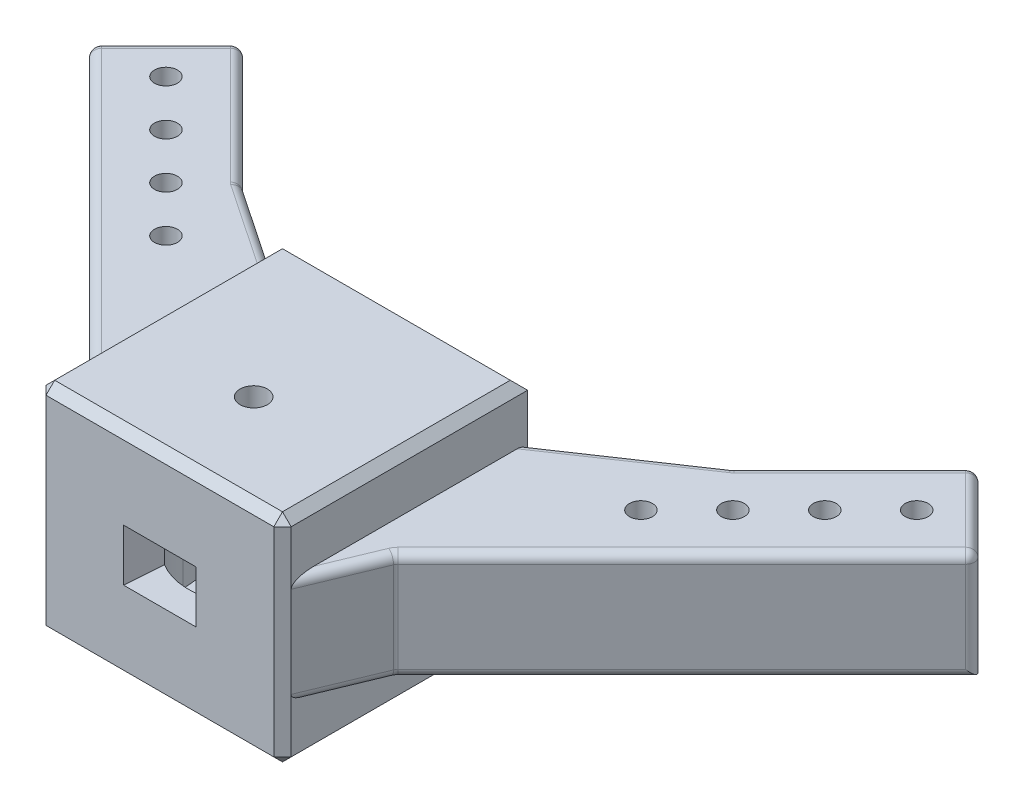
SolidWorks part; units mm, degrees
material "ABS"
ref_plane "前视基准面" through (0, 0, 0) normal (0, 0, 1) x (1, 0, 0)
ref_plane "上视基准面" through (0, 0, 0) normal (0, 1, 0) x (1, 0, 0)
ref_plane "右视基准面" through (0, 0, 0) normal (1, 0, 0) x (0, 0, -1)
other "Configuration Table"
sketch "草图1" plane through (0, 0, 0) normal (0, 1, 0) x (1, 0, 0)
  line L0 (0, 0) -> (0, -50000) construction
  line L1 (14.9366, -8.0239) -> (18.2843, 28.2843)
  line L2 (-28.2843, 28.2843) -> (28.2843, 28.2843)
  line L3 (-28.2843, 28.2843) -> (-28.2843, -28.2843)
  line L4 (-28.2843, -28.2843) -> (28.2843, -28.2843)
  line L5 (28.2843, 28.2843) -> (28.2843, -28.2843)
  line L6 (0, -28.2843) -> (0, 28.2843) construction
  line L7 (-28.2843, 0) -> (28.2843, 0) construction
  line L8 (-14.9366, -8.0239) -> (-18.2843, 28.2843)
  line L9 (-7.75, -19.4895) -> (-8.365, -28.2843)
  line L10 (7.75, -19.4895) -> (8.365, -28.2843)
  circle A0 centre (0, -6.6467) radius 3.15
  circle A1 centre (0, -6.6467) radius 15
  point P4 (0, 0)
  dimension "D1" = 6.3
  dimension "D2" = 30
  dimension "D3" = 56.5685
  dimension "D4" = 10.536
  dimension "D5" = 10
  dimension "D6" = 15.5
  dimension "D7" = 4
extrude "凸台-拉伸1" add sketch "草图1" along normal mid plane 50 contours A1 L8 L2 L3 L4 L5 L1 | A1 L1 L2 L8 | A1 A0 | A1 L8 L2 L3 L4 L9 | A1 L9 L4 L10 region at (0, 0, -16.4586) region at (20.9642, 0, 3.6641) region at (12.3502, 0, 14.3878) region at (0, 0, 24.6241) region at (-20.9642, 0, 3.6641)
extrude "切除-拉伸1" cut sketch "草图1<3>" against normal mid plane 40.3 contours A1 L1 L2 L8 | A1 A0 region at (0, 0, -16.4586) region at (12.3502, 0, 14.3878)
sketch "草图1<3>" plane through (0, 0, 0) normal (0, 1, 0) x (1, 0, 0) same geometry as "草图1"
sketch "草图3" plane through (0, 0, 0) normal (0, 1, 0) x (1, 0, 0)
  line L0 (28.2843, 19.0711) -> (84.8528, 75.6396)
  line L1 (84.8528, 75.6396) -> (102.5305, 57.9619)
  line L2 (102.5305, 57.9619) -> (28.2843, -16.2843)
  line L3 (28.2843, 19.0711) -> (28.2843, -16.2843) construction
  line L4 (28.2843, -28.2843) -> (28.2843, 28.2843)
  line L5 (28.2843, 28.2843) -> (-28.2843, 28.2843)
  line L6 (-28.2843, 28.2843) -> (-28.2843, -28.2843)
  line L7 (-28.2843, -28.2843) -> (28.2843, -28.2843)
  line L8 (28.2843, -28.2843) -> (28.2843, 28.2843)
  line L9 (28.2843, 28.2843) -> (-28.2843, 28.2843)
  line L11 (-28.2843, -28.2843) -> (28.2843, -28.2843)
  line L12 (28.2843, 28.2843) -> (28.2843, -28.2843) construction
  line L13 (93.6916, 66.8008) -> (28.2843, 1.3934) construction
  line L14 (28.2843, 28.2843) -> (56.5685, 47.3553)
  line L15 (28.2843, -26.2843) -> (35.3553, -9.2132)
  line L16 (0, 0) -> (0, -50000) construction
  line L17 (28.2843, 1.3934) -> (0, -26.8909) construction
  line L18 (-28.2843, 28.2843) -> (-28.2843, -28.2843)
  dimension "D2" = 80
  dimension "D3" = 25
  dimension "D4" = 45
  dimension "D5" = 132.5
  dimension "D6" = 12
  dimension "D7" = 2
  dimension "D8" = 10
  dimension "D1" = 0
extrude "凸台-拉伸2" add sketch "草图3" along normal mid plane 25 contours L8 L2 L1 L0 | L14 L8 L0 | L8 L2 region at (37.7124, 0, -31.5702) region at (61.187, 0, -33.4999) region at (30.6413, 0, 17.2606)
hole_wizard "Ø15.25 (15.25) 直径孔1" positions "草图5" profile "草图7" hole size "Ø15.25" standard "GB"
sketch "草图5" plane through (80.2462, 0, -80.2462) normal (0.7071, 0, -0.7071) x (-0.7071, 0, -0.7071)
  line L0 (-19.0147, 12.5) -> (-19.0147, -12.5) construction
  line L1 (-6.5147, 12.5) -> (-31.5147, 12.5) construction
  line L2 (-6.5147, -12.5) -> (-31.5147, -12.5) construction
  point P0 (-19.0147, 0)
sketch "草图7" plane through (93.6916, 0, -66.8008) normal (0, 1, 0) x (-0.7071, 0, -0.7071)
  line L0 (0, 0) -> (0, 75)
  line L1 (0, 75) -> (7.65, 75)
  line L2 (7.65, 75) -> (7.65, 0)
  line L5 (7.65, 0) -> (0, 0)
  line L10 (0, 75) -> (-7.65, 75) construction
  line L11 (0, -6.35) -> (0, 107.95) construction
  dimension "孔直径" = 15.3
  dimension "孔深度" = 75
  dimension "导头角度" = 180
sketch "草图8" plane through (17.1469, 12.5, 17.1469) normal (0, -1, 0) x (0.7071, 0, -0.7071)
  line L0 (113.4853, -5.2347) -> (20.9853, -5.2347) construction
  line L3 (113.4853, -17.7347) -> (113.4853, 7.2653) construction
  line L5 (40, -24.2494) -> (0, 15.7506) construction
  circle A0 centre (103.4853, -5.2347) radius 2.65
  circle A1 centre (88.4853, -5.2347) radius 2.65
  circle A2 centre (73.4853, -5.2347) radius 2.65
  circle A3 centre (58.4853, -5.2347) radius 2.65
  point P2 (3.2506, 0)
  point P3 (15.7506, 0)
  point P8 (108.2506, 0)
  point P15 (108.2506, 0)
  point P20 (105.8293, -6.7618)
  point P21 (108.3905, -0.1689)
  dimension "D1" = 5.3
  dimension "D4" = 15
  dimension "D3" = 10
  dimension "D2" = 4
extrude "切除-拉伸2" cut sketch "草图8" along normal up to surface (25 mm away) up to face at (55.9793, -12.5, -28.9573)
extrude "切除-拉伸3" cut sketch "草图1<4>" against normal mid plane 12 contours A1 L9 L4 L10 region at (0, 0, 24.6241)
sketch "草图1<4>" plane through (0, 0, 0) normal (0, 1, 0) x (1, 0, 0) same geometry as "草图1"
mirror "镜向3" about plane through (0, 0, 0) normal (1, 0, 0) of "切除-拉伸2", "Ø15.25 (15.25) 直径孔1", "凸台-拉伸2"
ref_axis "基准轴1" [suppressed] through (40.6586, 0, -6.3649) along (0.7071, 0, -0.7071)
ref_axis "基准轴2" [suppressed] through (-36.0865, 0, -1.7927) along (-0.7071, 0, -0.7071)
ref_point "点1" [suppressed]
ref_plane "基准面1" [suppressed] through (23.5117, 0, -23.5117) normal (0.7071, 0, -0.7071) x (-0.7071, 0, -0.7071)
fillet "圆角3" radius 2 12 edges at (42.4264, -12.5, -37.8198) (42.4264, 12.5, -37.8198) (70.7107, 12.5, -61.4975) (70.7107, -12.5, -61.4975) (68.9429, -12.5, -24.3744) (68.9429, 12.5, -24.3744) (56.5685, 0, -47.3553) (31.8198, 12.5, 17.7487) (31.8198, -12.5, 17.7487) (84.8528, 0, -75.6396) (35.3553, 0, 9.2132) (102.5305, 0, -57.9619)
fillet "圆角4" radius 2 3 edges at (93.6916, 12.5, -66.8008) (84.8528, 11.9142, -74.8112) (101.7021, 11.9142, -57.9619)
fillet "圆角5" radius 2 14 edges at (-93.6916, -12.5, -66.8008) (-102.5305, 0, -57.9619) (-93.6916, 12.5, -66.8008) (-84.8528, 0, -75.6396) (-42.4264, -12.5, -37.8198) (-42.4264, 12.5, -37.8198) (-70.7107, -12.5, -61.4975) (-70.7107, 12.5, -61.4975) (-68.9429, -12.5, -24.3744) (-68.9429, 12.5, -24.3744) (-56.5685, 0, -47.3553) (-31.8198, 12.5, 17.7487) (-31.8198, -12.5, 17.7487) (-35.3553, 0, 9.2132)
chamfer "倒角3" distance 1 angle 45 2 edges at (-99.101, 0, -61.3914) (88.2823, 0, -72.2101)
chamfer "倒角4" distance 2 angle 45 10 edges at (0, 25, -28.2843) (28.2843, 25, 0) (-28.2843, 25, 0) (0, 25, 28.2843) (0, -25, 28.2843) (-28.2843, -25, 0) (0, -25, -28.2843) (28.2843, -25, 0) (-28.2843, 0, 28.2843) (28.2843, 0, 28.2843)
